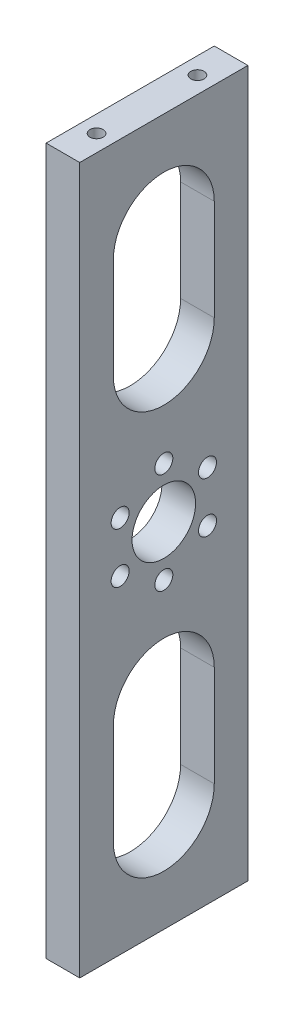
SolidWorks part; units mm, degrees
material "6061 Alloy"
ref_plane "Front Plane" through (0, 0, 0) normal (0, 0, 1) x (1, 0, 0)
ref_plane "Top Plane" through (0, 0, 0) normal (0, 1, 0) x (1, 0, 0)
ref_plane "Right Plane" through (0, 0, 0) normal (1, 0, 0) x (0, 0, -1)
sketch "Sketch1" plane through (0, 0, 0) normal (1, 0, 0) x (0, 0, -1)
  line L1 (-15.875, -66.675) -> (15.875, -66.675)
  line L2 (-15.875, -66.675) -> (-15.875, 66.675)
  line L3 (-15.875, 66.675) -> (15.875, 66.675)
  line L4 (15.875, -66.675) -> (15.875, 66.675)
  line L5 (-15.875, -66.675) -> (15.875, 66.675) construction
  line L6 (-15.875, 66.675) -> (15.875, -66.675) construction
  point P0 (0, 0)
  dimension "D1" = 31.75
  dimension "D2" = 133.35
extrude "Boss-Extrude1" add sketch "Sketch1" along normal mid plane 6.35
sketch "Sketch2" plane through (0, 66.675, 0) normal (0, 1, 0) x (1, 0, 0)
  line L0 (0, 9.525) -> (0, -9.525) construction
  line L1 (-3.175, 15.875) -> (-3.175, -15.875) construction
  line L2 (3.175, 15.875) -> (-3.175, 15.875) construction
  point P2 (0, 0)
  point P5 (-3.175, 0)
  point P8 (0, 15.875)
  point P10 (0, 9.525)
  point P11 (0, -9.525)
  dimension "D1" = 19.05
hole_wizard "M3x0.5 Tapped Hole1" positions "Sketch3" profile "Sketch5" tap size "M3x0.5" standard "ANSI Metric"
sketch "Sketch3" plane through (0, 66.675, 0) normal (0, 1, 0) x (1, 0, 0)
  point P0 (0, 9.525)
  point P3 (0, -9.525)
sketch "Sketch5" plane through (0, 66.675, -9.525) normal (1, 0, 0) x (0, 0, 1)
  line L0 (0, 0) -> (0, 13.4511)
  line L1 (0, 13.4511) -> (1.25, 12.7)
  line L2 (1.25, 12.7) -> (1.25, 0)
  line L5 (1.25, 0) -> (0, 0)
  line L10 (0, 13.4511) -> (-1.25, 12.7) construction
  line L11 (0, -6.35) -> (0, 107.95) construction
  dimension "Tap Drill Dia." = 2.5
  dimension "Tap Drill Depth" = 12.7
  dimension "Drill Angle" = 118
cosmetic thread "Hole Thread1" parameters "D1"=6.096, "D2"=3
cosmetic thread "Hole Thread2" parameters "D1"=6.096, "D2"=3
mirror "Mirror1" about plane through (0, 0, 0) normal (0, 1, 0) of "M3x0.5 Tapped Hole1"
cosmetic thread "Hole Thread3" parameters "D1"=6.096, "D2"=3
cosmetic thread "Hole Thread4" parameters "D1"=6.096, "D2"=3
sketch "Sketch6" plane through (-3.175, 0, 0) normal (-1, 0, 0) x (0, 0, 1)
  point P0 (0, 0)
hole_wizard "Ø12.0mm Dowel Hole1" positions "Sketch7" profile "Sketch8" hole size "Ø12.0" standard "ANSI Metric" end condition through all
sketch "Sketch7" plane through (-3.175, 0, 0) normal (-1, 0, 0) x (0, 0, 1)
  point P0 (0, 0)
sketch "Sketch8" plane through (-3.175, 0, 0) normal (0, 1, 0) x (0, 0, 1)
  line L0 (0, 0) -> (0, 6.35)
  line L1 (0, 6.35) -> (6, 6.35)
  line L2 (6, 6.35) -> (6, 0)
  line L5 (6, 0) -> (0, 0)
  line L11 (0, -6.35) -> (0, 107.95) construction
  dimension "Thru Hole Dia." = 12
  dimension "Thru Hole Depth" = 6.35
sketch "Sketch9" plane through (-3.175, 0, 0) normal (-1, 0, 0) x (0, 0, 1)
  point P0 (0, 9.525)
  point P1 (8.2489, 4.7625)
  point P3 (8.2489, -4.7625)
  point P5 (0, -9.525)
  point P7 (-8.2489, -4.7625)
  point P9 (-8.2489, 4.7625)
hole_wizard "CBORE for M3 SHCS1" positions "Sketch10" profile "Sketch11" counterbore size "M3" standard "ANSI Metric"
sketch "Sketch10" plane through (-3.175, 0, 0) normal (-1, 0, 0) x (0, 0, 1)
  point P0 (8.2489, -4.7625)
  point P3 (8.2489, 4.7625)
  point P6 (0, 9.525)
  point P9 (-8.2489, 4.7625)
  point P12 (-8.2489, -4.7625)
  point P15 (0, -9.525)
sketch "Sketch11" plane through (-3.175, -4.7625, 8.2489) normal (0, 1, 0) x (0, 0, 1)
  line L0 (0, 0) -> (0, 12.7)
  line L1 (0, 12.7) -> (1.7, 11.6785)
  line L2 (1.7, 11.6785) -> (1.7, 2)
  line L3 (1.7, 2) -> (2.25, 2)
  line L4 (2.25, 2) -> (2.25, 0)
  line L5 (2.25, 0) -> (0, 0)
  line L10 (0, 12.7) -> (-1.7, 11.6785) construction
  line L11 (0, -6.35) -> (0, 107.95) construction
  dimension "Hole Dia." = 3.4
  dimension "Hole Depth" = 12.7
  dimension "C'Bore Dia." = 4.5
  dimension "C'Bore Depth" = 2
  dimension "Drill Angle" = 118
sketch "Sketch12" plane through (3.175, 0, 0) normal (1, 0, 0) x (0, 0, -1)
  line L0 (0, 47.625) -> (0, 28.575) construction
  line L1 (9.525, 47.625) -> (9.525, 28.575)
  line L2 (-9.525, 47.625) -> (-9.525, 28.575)
  line L3 (0, -28.575) -> (0, -47.625) construction
  line L4 (9.525, -28.575) -> (9.525, -47.625)
  line L5 (-9.525, -28.575) -> (-9.525, -47.625)
  line L6 (0, 38.1) -> (0, -38.1) construction
  line L7 (3.4925, 0) -> (-3.4925, 0) construction
  arc A0 (9.525, 47.625) -> (-9.525, 47.625) centre (0, 47.625) ccw
  arc A1 (-9.525, 28.575) -> (9.525, 28.575) centre (0, 28.575) ccw
  arc A2 (9.525, -28.575) -> (-9.525, -28.575) centre (0, -28.575) ccw
  arc A3 (-9.525, -47.625) -> (9.525, -47.625) centre (0, -47.625) ccw
  point P3 (0, 38.1)
  point P8 (0, -38.1)
  point P20 (0, 0)
  dimension "D1" = 19.05
  dimension "D2" = 76.2
  dimension "D3" = 19.05
extrude "Cut-Extrude1" cut sketch "Sketch12" against normal through all contours L5 A3 L4 A2 | L1 A1 L2 A0 region at (3.175, -38.1, 0)
